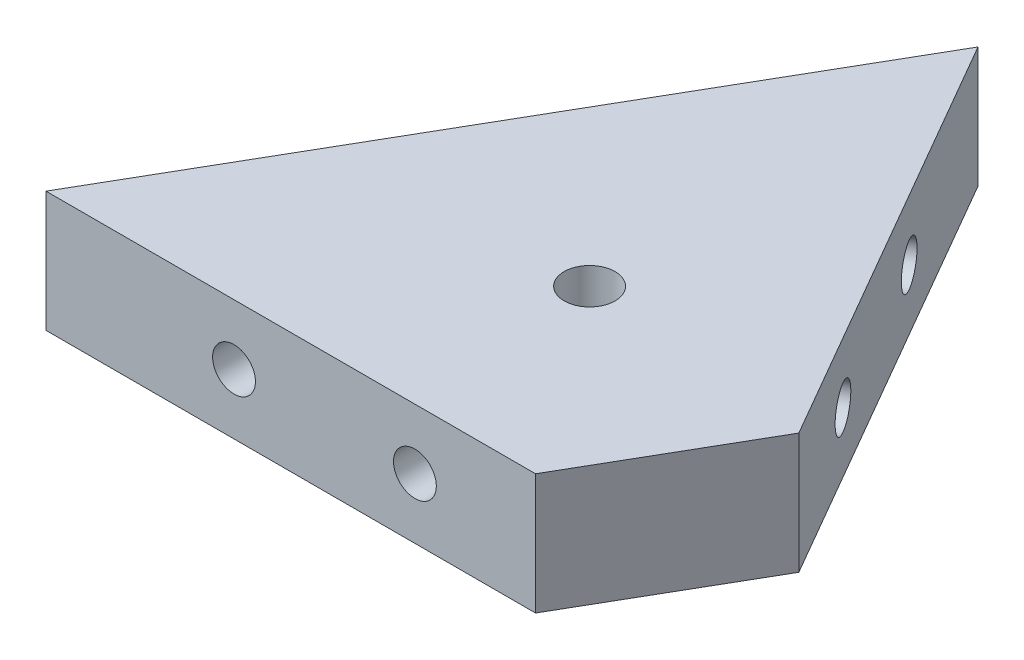
SolidWorks part; units mm, degrees
material "1023 Carbon Steel Sheet (SS)"
ref_plane "Front Plane" through (0, 0, 0) normal (0, 0, 1) x (1, 0, 0)
ref_plane "Top Plane" through (0, 0, 0) normal (0, 1, 0) x (1, 0, 0)
ref_plane "Right Plane" through (0, 0, 0) normal (1, 0, 0) x (0, 0, -1)
sketch "Sketch1" plane through (0, 0, 0) normal (0, 1, 0) x (1, 0, 0)
  line L0 (159.6594, -241.1624) -> (-297.5406, 22.8022) construction
  line L1 (-145.1406, 286.7667) -> (-449.9406, -241.1624) construction
  line L2 (-449.9406, -241.1624) -> (159.6594, -241.1624) construction
  line L3 (159.6594, -241.1624) -> (-145.1406, 286.7667) construction
  line L4 (93.6683, -241.1624) -> (93.6683, -203.0624) construction
  line L5 (119.0683, -241.1624) -> (129.2161, -223.5859)
  line L6 (55.5683, -241.1624) -> (55.5683, -181.0653) construction
  line L7 (15.9736, -241.1624) -> (51.8951, -178.9446)
  line L8 (15.9736, -241.1624) -> (119.0683, -241.1624)
  line L9 (51.8951, -178.9446) -> (129.2161, -223.5859)
  line L10 (93.6683, -203.0624) -> (55.5683, -203.0624) construction
  dimension "D1" = 609.6
  dimension "D2" = 38.1
  dimension "D3" = 25.4
  dimension "D4" = 38.1
  dimension "D6" = 40.5911
  dimension "D5" = 15.24
  dimension "D7" = 103.0947
extrude "Boss-Extrude1" add sketch "Sketch1" along normal blind 25.4
sketch "Sketch2" plane through (0, 0, 241.1624) normal (0, 0, 1) x (1, 0, 0)
  line L0 (15.9736, 0) -> (119.0683, 0) construction
  line L1 (15.9736, 0) -> (15.9736, 25.4) construction
  line L2 (119.0683, 0) -> (119.0683, 25.4) construction
  line L3 (15.9736, 25.4) -> (119.0683, 25.4) construction
  line L4 (15.9736, 0) -> (119.0683, 25.4) construction
  line L5 (119.0683, 0) -> (15.9736, 25.4) construction
  line L6 (93.6683, 25.4) -> (93.6683, 0) construction
  line L7 (55.5683, 0) -> (55.5683, 25.4) construction
  circle A0 centre (55.5683, 12.7) radius 4.5085
  circle A1 centre (93.6683, 12.7) radius 4.5085
  point P6 (67.521, 12.7)
  dimension "D4" = 9.017
  dimension "D5" = 9.017
  dimension "D1" = 25.4
  dimension "D2" = 25.4
  dimension "D3" = 38.1
extrude "Cut-Extrude1" cut sketch "Sketch2" against normal blind 12.7
sketch "Sketch3" plane through (0, 0, 228.4624) normal (0, 0, 1) x (1, 0, 0)
  circle A0 centre (55.5683, 12.7) radius 3.2639
  dimension "D1" = 6.5278
extrude "Cut-Extrude2" cut sketch "Sketch3" against normal blind 12.7
sketch "Sketch4" plane through (0, 0, 228.4624) normal (0, 0, 1) x (1, 0, 0)
  circle A0 centre (93.6683, 12.7) radius 3.2639
  dimension "D1" = 6.5278
extrude "Cut-Extrude3" cut sketch "Sketch4" against normal blind 12.7
mirror "Mirror1" about plane through (51.8951, 25.4, 178.9446) normal (-0.5, 0, 0.866) of "Boss-Extrude1", "Cut-Extrude1", "Cut-Extrude2", "Cut-Extrude3"
sketch "Sketch5" plane through (0, 25.4, 0) normal (0, 1, 0) x (1, 0, 0)
  line L0 (87.8165, -116.7268) -> (15.9736, -241.1624) construction
  line L1 (15.9736, -241.1624) -> (119.0683, -241.1624) construction
  line L2 (119.0683, -241.1624) -> (139.3639, -206.0094) construction
  line L3 (139.3639, -206.0094) -> (87.8165, -116.7268) construction
  line L4 (51.8951, -178.9446) -> (129.2161, -223.5859) construction
  circle A0 centre (90.5556, -201.2653) radius 5.3578
  dimension "D1" = 10.7156
extrude "Cut-Extrude4" cut sketch "Sketch5" against normal through all
ref_plane "Plane1" through (0, 0, 241.1624) normal (0, 0, 1) x (1, 0, 0)
equation "\"bplate_length\"= 24in"
equation "\"bplate_height\"= 6in"
equation "\"bplate_thickness\"= 0.5in"
equation "\"connector_plate_hole_diameter\"= 0.375in"
equation "\"connector_plate_hole_depth\"= 1in"
equation "\"connector_plate_thickness\"= 1in"
equation "\"D1@Sketch1\"=\"bplate_length\""
